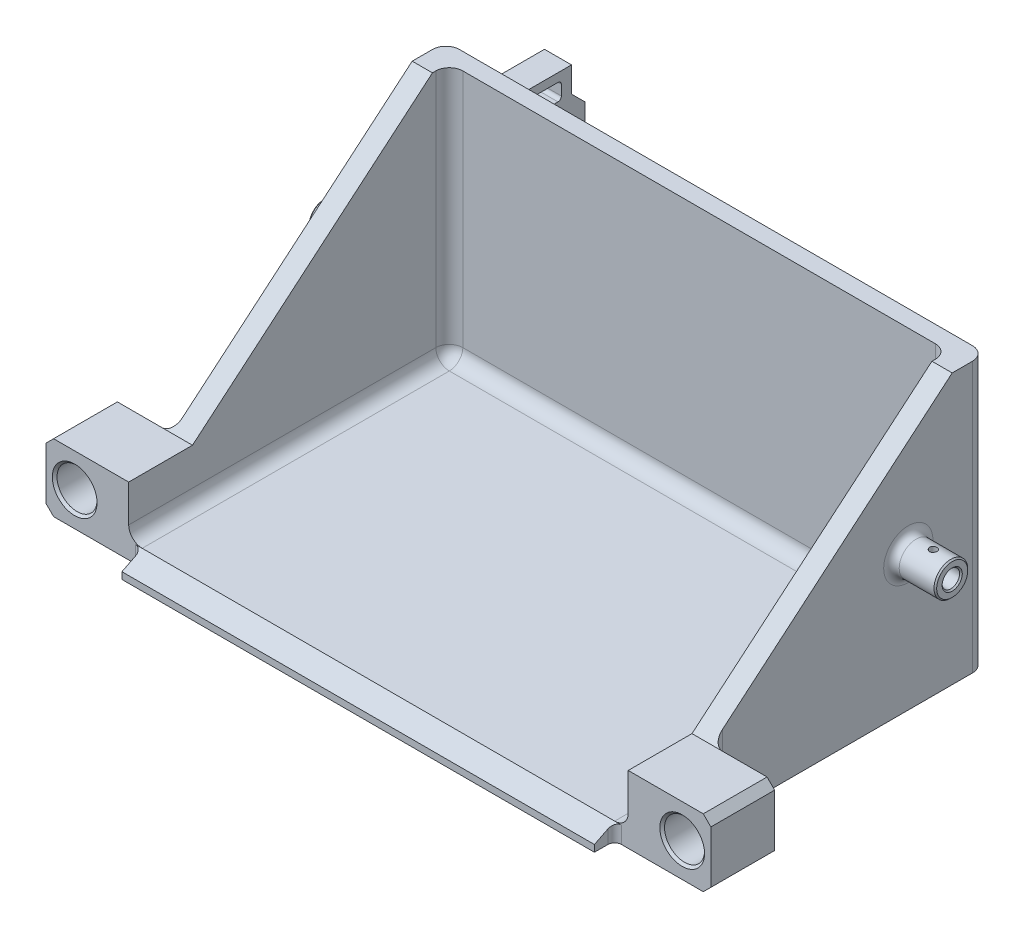
SolidWorks part; units mm, degrees
material "PLA"
ref_plane "Front Plane" through (0, 0, 0) normal (0, 0, 1) x (1, 0, 0)
ref_plane "Top Plane" through (0, 0, 0) normal (0, 1, 0) x (1, 0, 0)
ref_plane "Right Plane" through (0, 0, 0) normal (1, 0, 0) x (0, 0, -1)
sketch "Sketch1" plane through (0, 0, 0) normal (0, 1, 0) x (1, 0, 0)
  line L1 (-101.6, 63.5) -> (101.6, 63.5)
  line L2 (-101.6, 63.5) -> (-101.6, -63.5)
  line L3 (-101.6, -63.5) -> (101.6, -63.5)
  line L4 (101.6, 63.5) -> (101.6, -63.5)
  line L5 (-101.6, 63.5) -> (101.6, -63.5) construction
  line L6 (-101.6, -63.5) -> (101.6, 63.5) construction
  point P0 (0, 0)
  dimension "D1" = 203.2
  dimension "D2" = 127
extrude "Bucket_Base" add sketch "Sketch1" along normal mid plane 6.35
sketch "Sketch3" plane through (-101.6, 0, 0) normal (-1, 0, 0) x (0, 0, 1)
  line L0 (-63.5, 3.175) -> (-63.5, 98.425)
  line L1 (-63.5, 98.425) -> (-50.8, 98.425)
  line L3 (63.5, 3.175) -> (-63.5, 3.175)
  line L4 (-63.5, -3.175) -> (63.5, -3.175) construction
  line L5 (-50.8, 98.425) -> (39.497, 22.225)
  line L6 (39.497, 22.225) -> (63.5, 22.225)
  line L7 (63.5, 22.225) -> (63.5, 3.175)
  dimension "D1" = 101.6
  dimension "D2" = 12.7
  dimension "D3" = 25.4
  dimension "D4" = 24.003
extrude "Bucket_Sides" add sketch "Sketch3" against normal blind 7.62
mirror "Mirror1" about plane through (0, 0, 0) normal (1, 0, 0) of "Bucket_Sides"
sketch "Sketch4" plane through (0, 3.175, 0) normal (0, 1, 0) x (1, 0, 0)
  line L0 (-93.98, 63.5) -> (93.98, 63.5)
  line L1 (93.98, 63.5) -> (93.98, 57.15)
  line L2 (93.98, 57.15) -> (-93.98, 57.15)
  line L3 (-93.98, 57.15) -> (-93.98, 63.5)
  dimension "D1" = 6.35
extrude "Bucket_RearWall" add sketch "Sketch4" along normal up to surface (95.25 mm away) up to face at (-97.79, 98.425, -57.15)
sketch "Sketch6" plane through (101.6, 0, 0) normal (1, 0, 0) x (0, 0, -1)
  line L0 (-63.5, -3.175) -> (63.5, -3.175) construction
  line L2 (63.5, 98.425) -> (63.5, -3.175) construction
  circle A0 centre (34.29, 47.625) radius 3.2893
  circle A1 centre (34.29, 47.625) radius 6.35
  dimension "D1" = 6.5786
  dimension "D2" = 12.7
  dimension "D3" = 50.8
  dimension "D4" = 29.21
extrude "Shaft_Joint" add sketch "Sketch6" along normal blind 16.51
mirror "Mirror2" about plane through (0, 0, 0) normal (1, 0, 0) of "Shaft_Joint"
fillet "Fillet4" radius 2.921 2 edges at (101.6, 47.625, -27.94) (-101.6, 47.625, -40.64)
chamfer "Chamfer1" distance 0.508 angle 45 4 edges at (118.11, 47.625, -37.5793) (118.11, 47.625, -40.64) (-118.11, 47.625, -37.5793) (-118.11, 47.625, -40.64)
ref_plane "setscrew_lhs_plane" through (0, 53.975, 0) normal (0, 1, 0) x (1, 0, 0)
sketch "Sketch7" plane through (0, 53.975, 0) normal (0, 1, 0) x (1, 0, 0)
  line L0 (104.521, 27.94) -> (117.602, 27.94) construction
  line L1 (117.602, 40.64) -> (104.521, 40.64) construction
  line L2 (104.521, 27.94) -> (117.602, 27.94) construction
  line L3 (117.602, 40.64) -> (104.521, 40.64) construction
  line L4 (111.0615, 40.64) -> (111.0615, 27.94) construction
  circle A0 centre (111.0615, 34.29) radius 1.397
  dimension "D1" = 2.794
extrude "Cut-Extrude1" cut sketch "Sketch7" against normal blind 3.81
pattern_circular "CirPattern1" count 2 every 90 about axis through (118.11, 47.625, -34.29) along (-1, 0, 0) of "Cut-Extrude1"
mirror "Mirror3" about plane through (0, 0, 0) normal (1, 0, 0) of "CirPattern1"
ref_plane "Plane-BearingHousing" through (0, 0, 63.5) normal (0, 0, 1) x (1, 0, 0)
sketch "Sketch12" plane through (0, 0, 63.5) normal (0, 0, 1) x (1, 0, 0)
  line L0 (-101.6, 22.225) -> (-101.6, -3.175) construction
  line L1 (101.6, -3.175) -> (-101.6, -3.175) construction
  line L4 (-114.3, 9.525) -> (-101.6, 9.525) construction
  line L5 (-101.6, 22.225) -> (-101.6, -3.175)
  line L6 (-101.6, 22.225) -> (-125.095, 22.225)
  line L7 (-125.095, 22.225) -> (-125.095, -3.175)
  line L8 (-125.095, -3.175) -> (-101.6, -3.175)
  line L9 (0, -3.175) -> (0, 49996.825) construction
  line L10 (-101.6, 98.425) -> (-101.6, -3.175) construction
  line L11 (-101.6, -3.175) -> (101.6, -3.175) construction
  circle A0 centre (-114.3, 9.525) radius 7.5311
  point P15 (0, -3.175)
  dimension "D1" = 15.0622
  dimension "D2" = 23.495
  dimension "D3" = 114.3
  dimension "D4" = 12.7
extrude "Linear_Bearing_Housing" add sketch "Sketch12" against normal blind 24
mirror "Mirror4" about plane through (0, 0, 0) normal (1, 0, 0) of "Linear_Bearing_Housing"
chamfer "Chamfer2" distance 2.8575 angle 45 4 edges at (125.095, -3.175, 51.5) (125.095, 22.225, 51.5) (-125.095, -3.175, 51.5) (-125.095, 22.225, 51.5)
chamfer "Chamfer3" distance 0.889 angle 45 2 edges at (106.7689, 9.525, 63.5) (-106.7689, 9.525, 63.5)
sketch "ProfilSketch-Servo" plane through (-101.6, 0, 0) normal (-1, 0, 0) x (0, 0, 1)
  line L0 (63.5, 9.525) -> (39.5, 9.525) construction
  line L1 (48.1096, 9.525) -> (-49951.8904, 9.525) construction
  line L2 (-66.421, 72.39) -> (-86.4108, 72.39) construction
  line L3 (-86.4108, 72.39) -> (-86.4108, 32.385) construction
  line L4 (39.5, 19.3675) -> (39.5, -0.3175)
  line L5 (39.5, -0.3175) -> (63.5, -0.3175)
  line L6 (63.5, -0.3175) -> (63.5, 19.3675)
  line L7 (63.5, 19.3675) -> (39.5, 19.3675)
  line L8 (39.5, 19.3675) -> (39.5, -0.3175) construction
  line L9 (39.5, -0.3175) -> (63.5, -0.3175) construction
  line L10 (63.5, -0.3175) -> (63.5, 19.3675) construction
  line L11 (63.5, 19.3675) -> (39.5, 19.3675) construction
  line L12 (-86.4108, 32.385) -> (-66.421, 32.385) construction
  line L13 (-66.421, 32.385) -> (-66.421, 72.39) construction
  line L14 (-63.5, 98.425) -> (-63.5, -3.175) construction
  line L15 (-76.4159, 72.39) -> (-76.4159, 32.385) construction
  line L16 (-81.5213, 27.6352) -> (-71.3105, 27.6352) construction
  line L17 (-76.4159, 27.6352) -> (-76.4159, 32.385) construction
  line L18 (-86.4108, 52.3875) -> (-66.421, 52.3875) construction
  line L19 (-76.4159, 56.3784) -> (-76.4159, 24.3744) construction
  circle A0 centre (-76.4159, 40.3764) radius 3.175 construction
  circle A1 centre (-81.5213, 27.6352) radius 2.2606 construction
  circle A2 centre (-71.3105, 27.6352) radius 2.2606 construction
  circle A3 centre (-71.3105, 77.1398) radius 2.2606 construction
  circle A4 centre (-81.5213, 77.1398) radius 2.2606 construction
  point P32 (-76.4159, 40.3764)
  dimension "D6" = 6.35
  dimension "D10" = 4.5212
  dimension "D11" = 4.5212
  dimension "D2" = 40.005
  dimension "D3" = 19.9898
  dimension "D4" = 2.921
  dimension "D5" = 7.9914
  dimension "D7" = 22.86
  dimension "D8" = 4.7498
  dimension "D9" = 10.2108
  dimension "D12" = 32.004
  dimension "D1" = 0
ref_plane "Servo-Mount-Plane" through (-87.63, 0, 0) normal (-1, 0, 0) x (0, 0, 1)
sketch "Sketch14" plane through (-87.63, 0, 0) normal (-1, 0, 0) x (0, 0, 1)
  line L0 (-86.4108, 52.3875) -> (-66.421, 52.3875) construction
  line L1 (-86.4108, 52.3875) -> (-66.421, 52.3875) construction
  line L2 (-63.5, 22.9235) -> (-91.694, 22.9235)
  line L3 (-63.5, 98.425) -> (-63.5, -3.175) construction
  line L4 (-91.694, 22.9235) -> (-91.694, 81.8515)
  line L5 (-63.5, 22.9235) -> (-63.5, 81.8515)
  line L7 (-66.04, 72.9615) -> (-66.04, 31.8135)
  line L8 (-66.04, 31.8135) -> (-86.614, 31.8135)
  line L9 (-86.614, 31.8135) -> (-86.614, 72.9615)
  line L12 (-63.5, 81.8515) -> (-91.694, 81.8515)
  line L13 (-66.04, 72.9615) -> (-86.614, 72.9615)
  line L14 (-76.327, 72.9615) -> (-76.327, 31.8135) construction
  circle A4 centre (-81.534, 77.1525) radius 1.6129
  circle A5 centre (-71.12, 77.1525) radius 1.6129
  circle A6 centre (-71.12, 27.6225) radius 1.6129
  circle A7 centre (-81.534, 27.6225) radius 1.6129
  point P19 (-91.694, 52.3875)
  point P30 (-63.5, 52.3875)
  point P31 (-66.04, 52.3875)
  point P32 (-86.614, 52.3875)
  dimension "D2" = 41.148
  dimension "D3" = 2.54
  dimension "D6" = 3.2258
  dimension "D8" = 49.53
  dimension "D1" = 20.574
  dimension "D4" = 5.08
  dimension "D5" = 8.89
  dimension "D7" = 10.414
extrude "Servo-Mount" add sketch "Sketch14" against normal blind 10.16
ref_plane "MidPlane-ServoHousing" through (0, 0, -76.327) normal (0, 0, -1) x (-1, 0, 0)
ref_plane "MidPlane2-ServoHousing" through (0, 52.3875, 0) normal (0, 1, 0) x (1, 0, 0)
fillet "Fillet5" radius 1.27 2 edges at (-77.47, 52.3875, -63.5) (-87.63, 52.3875, -63.5)
fillet "Fillet6" radius 5.08 9 edges at (-93.98, 50.8, -57.15) (93.98, 50.8, -57.15) (93.98, 3.175, 3.175) (-93.98, 3.175, 3.175) (0, 3.175, -57.15) (101.6, 47.625, -63.5) (-101.6, 47.625, -63.5) (-82.55, 22.9235, -63.5) (-82.55, 81.8515, -63.5)
fillet "Fillet7" radius 3.81 2 edges at (101.6, 9.525, 39.5) (-101.6, 9.525, 39.5)
chamfer "Chamfer4" distance 5.08 angle 45 2 edges at (-82.55, 22.9235, -91.694) (-82.55, 81.8515, -91.694)
sketch "Sketch15" plane through (0, 0, 0) normal (1, 0, 0) x (0, 0, -1)
  line L0 (-63.5, 3.175) -> (52.07, 3.175) construction
  line L1 (-63.5, 3.175) -> (52.07, 3.175) construction
  line L2 (-63.5, 3.175) -> (-71.12, -0.635)
  line L3 (-71.12, -0.635) -> (-71.12, -3.175)
  line L4 (-71.12, -3.175) -> (-63.5, -3.175)
  line L5 (-63.5, 3.175) -> (-63.5, -3.175)
  dimension "D1" = 2.54
  dimension "D2" = 7.62
extrude "Boss-Extrude2" add sketch "Sketch15" along normal mid plane 177.8
fillet "Fillet8" radius 2.54 2 edges at (88.9, 0, 63.5) (-88.9, 0, 63.5)
sketch "Sketch16" plane through (0, 52.3875, 0) normal (0, 1, 0) x (1, 0, 0)
  line L0 (-33.02, 63.5) -> (-33.02, 69.85)
  line L1 (96.52, 63.5) -> (-96.52, 63.5) construction
  line L2 (-33.02, 69.85) -> (-48.26, 69.85)
  line L3 (-48.26, 69.85) -> (-48.26, 66.04)
  line L4 (-48.26, 66.04) -> (-52.07, 66.04)
  line L5 (-52.07, 66.04) -> (-52.07, 73.66)
  line L6 (-52.07, 73.66) -> (-29.21, 73.66)
  line L7 (-29.21, 73.66) -> (-29.21, 63.5)
  line L8 (-33.02, 63.5) -> (-29.21, 63.5)
  line L9 (-77.47, 68.58) -> (-77.47, 86.614) construction
  dimension "D1" = 6.35
  dimension "D2" = 3.81
  dimension "D3" = 2.54
  dimension "D4" = 3.81
  dimension "D5" = 3.81
  dimension "D6" = 25.4
  dimension "D7" = 15.24
extrude "Boss-Extrude3" add sketch "Sketch16" along normal mid plane 13.97
fillet "Fillet9" radius 1.905 6 edges at (-48.26, 52.3875, -69.85) (-33.02, 52.3875, -69.85) (-33.02, 52.3875, -63.5) (-31.115, 45.4025, -63.5) (-31.115, 59.3725, -63.5) (-29.21, 52.3875, -63.5)
sketch "Sketch17" plane through (-87.63, 0, 0) normal (-1, 0, 0) x (0, 0, 1)
  line L0 (-86.614, 81.8515) -> (-86.614, 91.3765)
  line L1 (-68.58, 81.8515) -> (-86.614, 81.8515) construction
  line L2 (-86.614, 91.3765) -> (-69.469, 91.3765)
  line L3 (-69.469, 91.3765) -> (-69.469, 85.6615)
  line L4 (-69.469, 85.6615) -> (-72.644, 85.6615)
  line L5 (-72.644, 85.6615) -> (-72.644, 88.2015)
  line L6 (-72.644, 88.2015) -> (-82.804, 88.2015)
  line L7 (-82.804, 88.2015) -> (-82.804, 81.8515)
  line L8 (-82.804, 81.8515) -> (-86.614, 81.8515)
  dimension "D1" = 3.81
  dimension "D2" = 3.175
  dimension "0.4" = 10.16
  dimension "D4" = 3.175
  dimension "D5" = 6.35
  dimension "D6" = 3.81
extrude "Boss-Extrude4" add sketch "Sketch17" against normal up to surface (10.16 mm away) up to face at (-77.47, 27.6225, -83.1469)
fillet "Fillet10" radius 1.27 4 edges at (-82.55, 81.8515, -86.614) (-82.55, 88.2015, -72.644) (-82.55, 88.2015, -82.804) (-82.55, 81.8515, -82.804)
fillet "Fillet11" radius 0.635 4 edges at (-82.55, 72.9615, -66.04) (-82.55, 72.9615, -86.614) (-82.55, 31.8135, -86.614) (-82.55, 31.8135, -66.04)
sketch "Sketch18" plane through (-87.63, 0, 0) normal (-1, 0, 0) x (0, 0, 1)
  line L0 (-76.327, 72.9615) -> (-76.327, 31.8135) construction
  line L1 (-66.675, 72.9615) -> (-85.979, 72.9615) construction
  line L2 (-85.979, 31.8135) -> (-66.675, 31.8135) construction
  line L3 (-79.756, 72.9615) -> (-79.756, 76.3143)
  line L4 (-79.756, 76.3143) -> (-72.898, 76.3143)
  line L5 (-72.898, 72.9615) -> (-79.756, 72.9615)
  line L6 (-72.898, 72.9615) -> (-72.898, 76.3143)
  line L7 (-76.327, 52.3875) -> (-86.614, 52.3875) construction
  line L8 (-86.614, 72.3265) -> (-86.614, 32.4485) construction
  line L9 (-72.898, 31.8135) -> (-72.898, 28.4607)
  line L10 (-72.898, 31.8135) -> (-79.756, 31.8135)
  line L11 (-79.756, 28.4607) -> (-72.898, 28.4607)
  line L12 (-79.756, 31.8135) -> (-79.756, 28.4607)
  point P11 (-76.327, 76.3143)
  point P19 (-76.327, 28.4607)
  dimension "D1" = 3.3528
  dimension "D2" = 6.858
extrude "Servo-Wire-Relief" cut sketch "Sketch18" against normal through all
fillet "Fillet12" radius 1.016 4 edges at (-82.55, 28.4607, -79.756) (-82.55, 28.4607, -72.898) (-82.55, 76.3143, -79.756) (-82.55, 76.3143, -72.898)
chamfer "Chamfer5" distance 0.635 angle 45 4 edges at (-82.55, 31.8135, -72.898) (-82.55, 31.8135, -79.756) (-82.55, 72.9615, -79.756) (-82.55, 72.9615, -72.898)
equation "\"D11@ProfilSketch-Servo\"=\"D10@ProfilSketch-Servo\""
